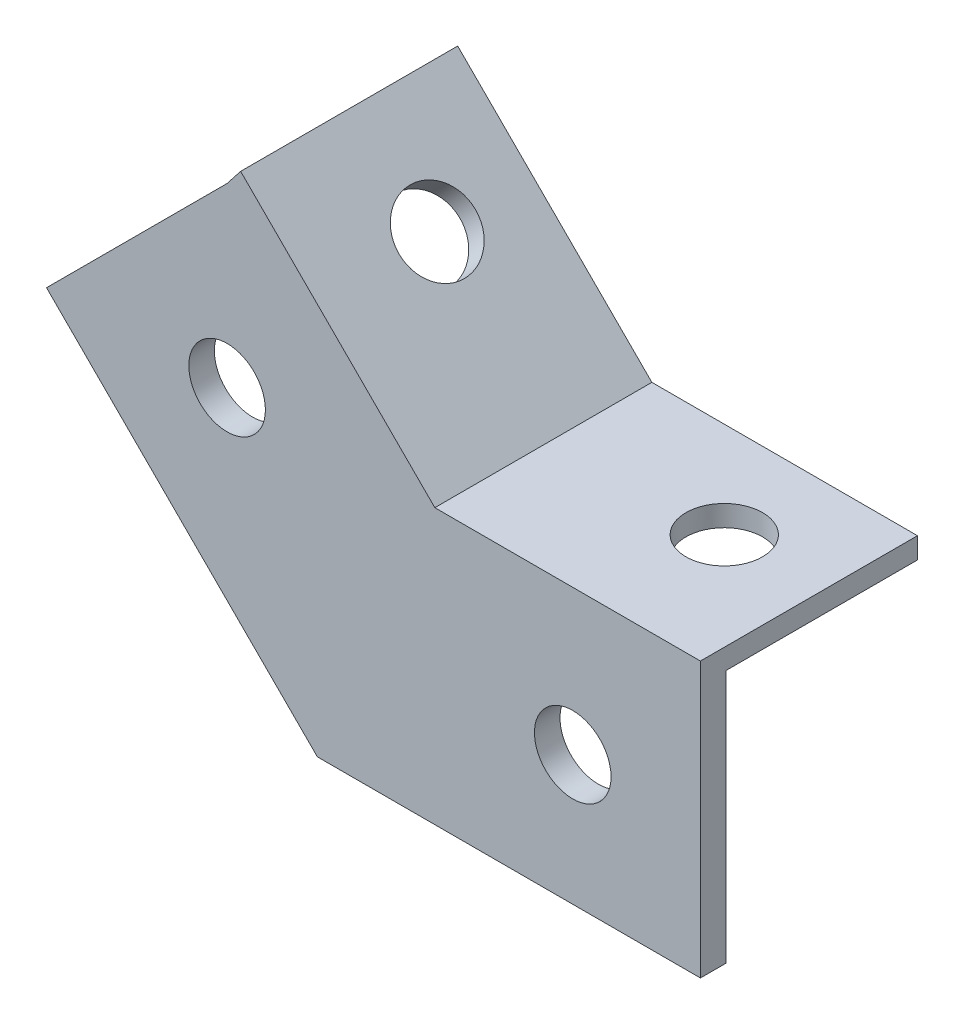
SolidWorks part; units mm, degrees
ref_plane "Plano frontal" through (0, 0, 0) normal (0, 0, 1) x (1, 0, 0)
ref_plane "Plano superior" through (0, 0, 0) normal (0, 1, 0) x (1, 0, 0)
ref_plane "Plano direito" through (0, 0, 0) normal (1, 0, 0) x (0, 0, -1)
sketch "Esboço1" plane through (0, 0, 0) normal (0, 0, 1) x (1, 0, 0)
  line L37 (-42.3663, -154.1466) -> (-42.3663, -174)
  line L44 (-42.3663, -174) -> (-72.3663, -174)
  line L46 (-42.3663, -154.1466) -> (-63.9354, -154.1466)
  line L47 (-72.3663, -174) -> (-93.5795, -152.7868)
  line L49 (-93.5795, -152.7868) -> (-79.4373, -138.6447)
  line L50 (-79.4373, -138.6447) -> (-63.9354, -154.1466)
  circle A4 centre (-79.4373, -152.4937) radius 3
  circle A6 centre (-52.3663, -163.8534) radius 3
  point P0 (-53.8789, -163.8534)
  point P47 (0, 0)
  point P52 (-63.7889, -154.5984)
extrude "Ressalto-extrusão1" add sketch "Esboço1" along normal blind 2
sketch "Esboço5" plane through (0, 0, 2) normal (0, 0, 1) x (1, 0, 0)
  line L0 (-79.4373, -138.6447) -> (-78.3767, -137.2909)
  line L1 (-63.1676, -152.5) -> (-42.3663, -152.5)
  line L3 (-42.3663, -154.1466) -> (-42.3663, -152.5)
  line L4 (-63.1676, -152.5) -> (-78.3767, -137.2909)
  line L6 (-63.9354, -154.1466) -> (-63.1676, -152.5)
  line M10 (-42.3663, -154.1466) -> (-63.9354, -154.1466)
  line M11 (-63.9354, -154.1466) -> (-79.4373, -138.6447)
extrude "Ressalto-extrusão2" add sketch "Esboço5" against normal blind 17 contours L6 L4 L0 M11 | L6 L3 L1 M10 region at (-71.2307, -145.6479, 2) region at (-52.9601, -153.3283, 2)
sketch "Esboço6" plane through (-109.041, -109.041, 0) normal (-0.7071, -0.7071, 0) x (-0.7071, 0.7071, 0)
  circle A0 centre (-50, 7.5) radius 3
sketch "Esboço7" plane through (0, -154.1466, 0) normal (0, -1, 0) x (1, 0, 0)
  circle A0 centre (-50, -7.5) radius 3
extrude "Corte-extrusão1" cut sketch "Esboço6" against normal up to next contours A0
extrude "Corte-extrusão2" cut sketch "Esboço7" against normal up to next contours A0
